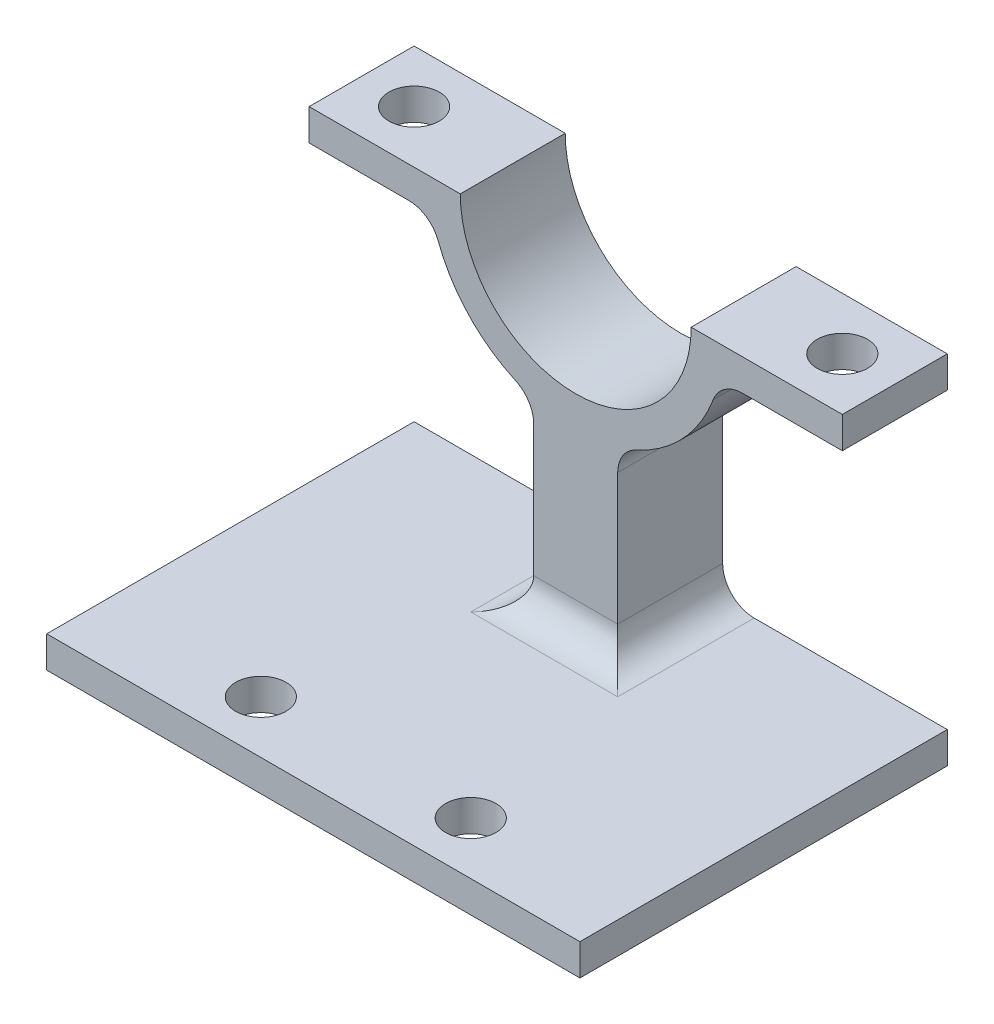
SolidWorks part; units mm, degrees
material "Windform GT"
ref_plane "Front Plane" through (0, 0, 0) normal (0, 0, 1) x (1, 0, 0)
ref_plane "Top Plane" through (0, 0, 0) normal (0, 1, 0) x (1, 0, 0)
ref_plane "Right Plane" through (0, 0, 0) normal (1, 0, 0) x (0, 0, -1)
sketch "Sketch1" plane through (0, 0, 0) normal (0, 0, 1) x (1, 0, 0)
  line L0 (5.5, 0) -> (12.7, 0)
  line L1 (12.7, 0) -> (12.7, -1.5)
  line L2 (12.7, -1.5) -> (6.8374, -1.5)
  line L5 (0, 0) -> (0, -7) construction
  line L7 (-12.7, -1.5) -> (-6.8374, -1.5)
  line L8 (-12.7, 0) -> (-12.7, -1.5)
  line L9 (-5.5, 0) -> (-12.7, 0)
  arc A2 (5.5, 0) -> (-5.5, 0) centre (0, 0) cw
  arc A3 (-6.8374, -1.5) -> (6.8374, -1.5) centre (0, 0) ccw
  dimension "D1" = 7
  dimension "D2" = 5.5
  dimension "D3" = 12.7
  dimension "D4" = 1.5
extrude "Boss-Extrude1" add sketch "Sketch1" along normal mid plane 5
sketch "Sketch2" plane through (0, 0, 0) normal (0, 1, 0) x (1, 0, 0)
  line L0 (12.7, 0) -> (-12.7, 0) construction
  line L1 (-12.7, -2.5) -> (-12.7, 2.5) construction
  line L2 (0, 0) -> (0, 2.5) construction
  line L3 (5.5, 2.5) -> (-5.5, 2.5) construction
  circle A0 centre (-10.2, 0) radius 1.2
  circle A1 centre (10.2, 0) radius 1.2
  dimension "D1" = 2.5
  dimension "D2" = 2.4
extrude "Cut-Extrude1" cut sketch "Sketch2" against normal through all
sketch "Sketch3" plane through (0, 0, 0) normal (0, 1, 0) x (1, 0, 0)
  line L0 (5.5, -2.5) -> (5.5, 2.5) construction
  line L1 (-2, -2.5) -> (2, -2.5)
  line L2 (-2, -2.5) -> (-2, 2.5)
  line L3 (-2, 2.5) -> (2, 2.5)
  line L4 (2, -2.5) -> (2, 2.5)
  line L5 (-2, -2.5) -> (2, 2.5) construction
  line L6 (-2, 2.5) -> (2, -2.5) construction
  point P0 (0, 0)
  dimension "D1" = 4
extrude "Boss-Extrude2" add sketch "Sketch3" along normal up to surface (8.7918 mm away) from offset 15.5 up to face at (0, -4.25, 0) offset against normal yes
sketch "Sketch4" plane through (0, -15.5, 0) normal (0, -1, 0) x (1, 0, 0)
  line L0 (0, 0) -> (0, 15) construction
  line L6 (0, 0) -> (0, -2.5) construction
  line L7 (2, -2.5) -> (-2, -2.5) construction
  line L12 (12.7, -2.5) -> (-12.7, -2.5)
  line L22 (-12.7, -2.5) -> (-12.7, 15)
  line L23 (-12.7, 15) -> (12.7, 15)
  line L24 (12.7, -2.5) -> (12.7, 15)
  line L27 (-5.5, 2.5) -> (-12.7, 2.5) construction
  point P9 (0, 0)
  point P10 (-12.7, -2.5)
  point P11 (12.9137, -2.5)
  dimension "D1" = 12.5
extrude "Boss-Extrude3" add sketch "Sketch4" along normal blind 1.5
fillet "Fillet1" radius 1.5 7 edges at (2, -15.5, 0) (2, -6.7082, 0) (6.8374, -1.5, 0) (-6.8374, -1.5, 0) (-2, -6.7082, 0) (-2, -15.5, 0) (0, -15.5, 2.5)
sketch "Sketch5" plane through (0, 0, 0) normal (0, 1, 0) x (1, 0, 0)
  line L0 (-5, 2.5) -> (-5, -15) construction
  line L1 (12.7, -15) -> (-12.7, -15) construction
  line L2 (0, 2.5) -> (0, -15) construction
  line L3 (5, 2.5) -> (5, -15) construction
  line L4 (5.5, 2.5) -> (-5.5, 2.5) construction
  line L5 (-5.5, 2.5) -> (-12.7, 2.5) construction
  circle A0 centre (-5, -12.5) radius 1.2
  circle A3 centre (5, -12.5) radius 1.2
  dimension "D2" = 2.4
  dimension "D1" = 2.5
  dimension "D4" = 5
extrude "Cut-Extrude2" cut sketch "Sketch5" against normal through all
